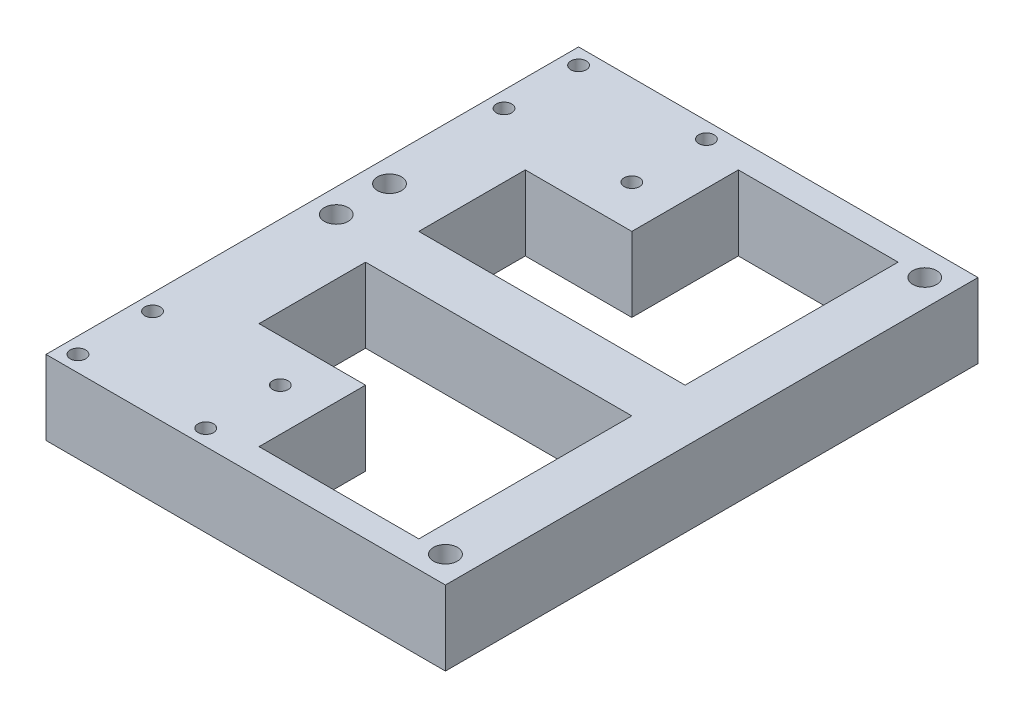
SolidWorks part; units mm, degrees
ref_plane "前视基准面" through (0, 0, 0) normal (0, 0, 1) x (1, 0, 0)
ref_plane "上视基准面" through (0, 0, 0) normal (0, 1, 0) x (1, 0, 0)
ref_plane "右视基准面" through (0, 0, 0) normal (1, 0, 0) x (0, 0, -1)
other "Configuration Table"
sketch "草图1" plane through (0, 0, 0) normal (0, 1, 0) x (1, 0, 0)
  line L1 (0, 0) -> (-75, 0)
  line L2 (0, 0) -> (0, 100)
  line L3 (0, 100) -> (-75, 100)
  line L4 (-75, 0) -> (-75, 100)
  dimension "D1" = 100
  dimension "D2" = 75
extrude "凸台-拉伸1" add sketch "草图1" along normal blind 16
sketch "草图6" plane through (0, 16, 0) normal (0, 1, 0) x (1, 0, 0)
  line L0 (-75, 100) -> (-75, 0) construction
  line L1 (-40, 45) -> (-5, 45)
  line L2 (-40, 25) -> (-40, 5)
  line L3 (-40, 5) -> (-5, 5)
  line L4 (-5, 45) -> (-5, 5)
  line L5 (0, 0) -> (0, 100) construction
  line L6 (-75, 0) -> (0, 0) construction
  line L7 (-75, 50) -> (-60.5255, 50) construction
  line L8 (-40, 95) -> (-5, 95)
  line L9 (-5, 55) -> (-5, 95)
  line L10 (-40, 55) -> (-5, 55)
  line L11 (-40, 75) -> (-40, 95)
  line L12 (-40, 75) -> (-70, 75)
  line L13 (-40, 45) -> (-70, 45)
  line L15 (-40, 25) -> (-70, 25)
  line L16 (-70, 45) -> (-70, 25)
  line L17 (-40, 55) -> (-70, 55)
  line L18 (-70, 55) -> (-70, 75)
  dimension "D1" = 35
  dimension "D2" = 5
  dimension "D3" = 5
  dimension "D4" = 40
  dimension "D5" = 30
  dimension "D6" = 20
extrude "切除-拉伸5" cut sketch "草图6" against normal up to next
sketch "草图8" plane through (0, 16, 0) normal (0, 1, 0) x (1, 0, 0)
  line L0 (-75, 100) -> (-72, 100) construction
  line L1 (0, 100) -> (-75, 100) construction
  line L2 (-72, 100) -> (-72, 97) construction
  line L3 (-72, 97) -> (-48, 97) construction
  line L4 (-48, 97) -> (-48, 83) construction
  line L5 (-48, 83) -> (-72, 83) construction
  line L6 (-75, 50) -> (-51.1245, 50) construction
  line L7 (-75, 100) -> (-75, 0) construction
  line L8 (-48, 17) -> (-72, 17) construction
  line L9 (-48, 3) -> (-48, 17) construction
  line L10 (-72, 3) -> (-48, 3) construction
  line L11 (-72, 0) -> (-72, 3) construction
  line L12 (-75, 0) -> (-72, 0) construction
  circle A0 centre (-72, 97) radius 1.45
  circle A1 centre (-72, 83) radius 1.45
  circle A2 centre (-48, 97) radius 1.45
  circle A3 centre (-48, 83) radius 1.45
  circle A4 centre (-48, 17) radius 1.45
  circle A5 centre (-48, 3) radius 1.45
  circle A6 centre (-72, 17) radius 1.45
  circle A7 centre (-72, 3) radius 1.45
  dimension "D6" = 2.9
  dimension "D7" = 2.9
  dimension "D8" = 2.9
  dimension "D9" = 2.9
  dimension "D1" = 3
  dimension "D2" = 3
  dimension "D3" = 24
  dimension "D4" = 14
  dimension "D5" = 24
extrude "切除-拉伸7" cut sketch "草图8" against normal through all
sketch "草图9" plane through (-5, 0, 0) normal (-1, 0, 0) x (0, 0, 1)
  line L0 (-45, 0) -> (-5, 0) construction
  line L1 (-5, 0) -> (-5, 16) construction
  line L2 (-5, 16) -> (-45, 16) construction
  line L3 (-45, 16) -> (-45, 0) construction
  line L4 (-95, 0) -> (-55, 0) construction
  line L5 (-55, 0) -> (-55, 16) construction
  line L6 (-55, 16) -> (-95, 16) construction
  line L7 (-95, 16) -> (-95, 0) construction
  line L8 (-45, 0) -> (-5, 0)
  line L9 (-5, 0) -> (-5, 16)
  line L10 (-5, 16) -> (-45, 16)
  line L11 (-45, 16) -> (-45, 0)
  line L12 (-95, 0) -> (-55, 0)
  line L13 (-55, 0) -> (-55, 16)
  line L14 (-55, 16) -> (-95, 16)
  line L15 (-95, 16) -> (-95, 0)
extrude "凸台-拉伸2" add sketch "草图9" along normal blind 5
sketch "草图10" plane through (0, 16, 0) normal (0, 1, 0) x (1, 0, 0)
  line L0 (0, 100) -> (0, 95) construction
  line L1 (0, 0) -> (0, 100) construction
  line L2 (0, 95) -> (-5, 95) construction
  line L3 (0, 50) -> (-16.1785, 50) construction
  circle A0 centre (-5, 95) radius 2.25
  circle A1 centre (-5, 5) radius 2.25
  dimension "D3" = 4.5
  dimension "D1" = 5
  dimension "D2" = 5
extrude "切除-拉伸8" cut sketch "草图10" against normal blind 5
sketch "草图11" plane through (0, 0, 0) normal (0, -1, 0) x (1, 0, 0)
  circle A0 centre (-5, -95) radius 2.25 construction
  circle A1 centre (-5, -5) radius 2.25 construction
  circle A2 centre (-5, -95) radius 2.25
  circle A3 centre (-5, -5) radius 2.25
extrude "切除-拉伸9" cut sketch "草图11" against normal blind 7
sketch "草图12" plane through (-70, 0, 0) normal (1, 0, 0) x (0, 0, -1)
  line L0 (25, 0) -> (45, 0) construction
  line L1 (45, 0) -> (45, 16) construction
  line L2 (45, 16) -> (25, 16) construction
  line L3 (25, 16) -> (25, 0) construction
  line L4 (55, 0) -> (75, 0) construction
  line L5 (75, 0) -> (75, 16) construction
  line L6 (75, 16) -> (55, 16) construction
  line L7 (55, 16) -> (55, 0) construction
  line L8 (25, 0) -> (45, 0)
  line L9 (45, 0) -> (45, 16)
  line L10 (45, 16) -> (25, 16)
  line L11 (25, 16) -> (25, 0)
  line L12 (55, 0) -> (75, 0)
  line L13 (75, 0) -> (75, 16)
  line L14 (75, 16) -> (55, 16)
  line L15 (55, 16) -> (55, 0)
extrude "凸台-拉伸3" add sketch "草图12" along normal blind 10
sketch "草图13" plane through (0, 16, 0) normal (0, 1, 0) x (1, 0, 0)
  line L0 (-75, 50) -> (-70.5, 50) construction
  line L1 (-75, 100) -> (-75, 0) construction
  line L3 (-70.5, 50) -> (-70.5, 60) construction
  circle A0 centre (-70.5, 50) radius 2.25
  circle A1 centre (-70.5, 60) radius 2.25
  dimension "D4" = 4.5
  dimension "D5" = 4.5
  dimension "D3" = 10
  dimension "D6" = 4.5
  dimension "D1" = 4.5
  dimension "D2" = 10
extrude "切除-拉伸10" cut sketch "草图13" against normal blind 5
sketch "草图14" plane through (0, 0, 0) normal (0, -1, 0) x (1, 0, 0)
  line L4 (0, -100) -> (0, 0)
  line L5 (0, 0) -> (-75, 0)
  line L6 (-75, 0) -> (-75, -100)
  line L7 (-75, -100) -> (0, -100)
  line L8 (0, -100) -> (0, 0)
  line L9 (0, 0) -> (-75, 0)
  line L10 (-75, 0) -> (-75, -100)
  line L11 (-75, -100) -> (0, -100)
  dimension "D1" = 0
extrude "切除-拉伸11" cut sketch "草图14" against normal blind 2
